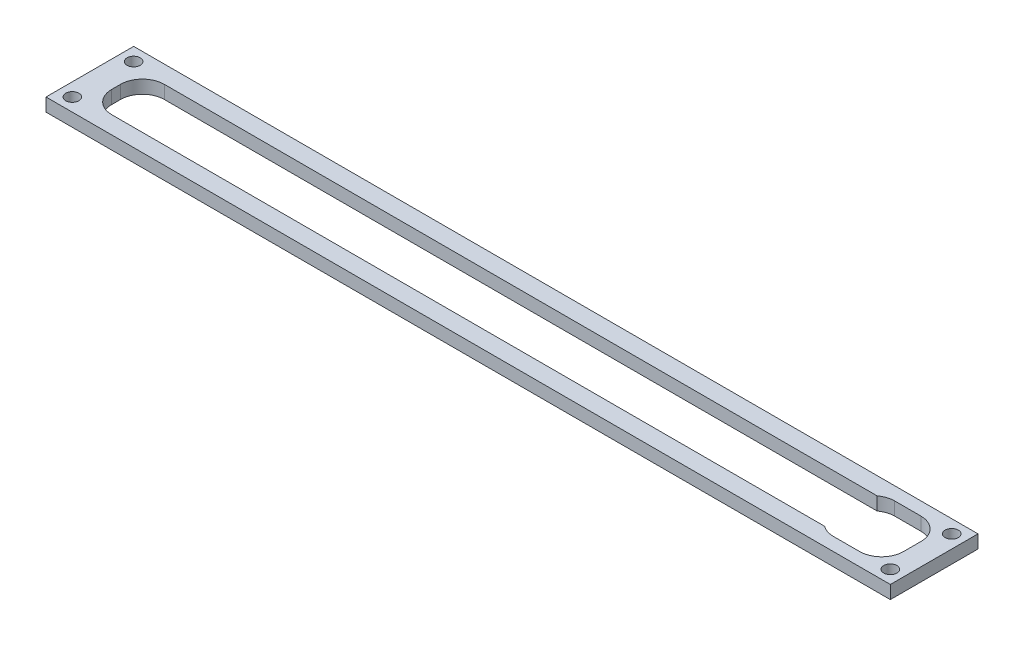
SolidWorks part; units mm, degrees
ref_plane "Front Plane" through (0, 0, 0) normal (0, 0, 1) x (1, 0, 0)
ref_plane "Top Plane" through (0, 0, 0) normal (0, 1, 0) x (1, 0, 0)
ref_plane "Right Plane" through (0, 0, 0) normal (1, 0, 0) x (0, 0, -1)
sketch "Sketch1" plane through (0, 0, 0) normal (0, 1, 0) x (1, 0, 0)
  line L0 (96.3209, 20) -> (96.3209, 0) construction
  line L1 (0, 0) -> (192.6417, 0)
  line L2 (0, 0) -> (0, 20)
  line L3 (0, 20) -> (192.6417, 20)
  line L4 (192.6417, 0) -> (192.6417, 20)
  line L5 (0, 10) -> (192.6417, 10) construction
  line L6 (96.3209, 16) -> (96.3209, 4) construction
  line L7 (6, 16) -> (186.6417, 16)
  line L8 (6, 16) -> (6, 4)
  line L9 (6, 4) -> (186.6417, 4)
  line L10 (186.6417, 16) -> (186.6417, 4)
  line L11 (6, 10) -> (186.6417, 10) construction
  circle A0 centre (3, 17) radius 1.5
  circle A1 centre (3, 3) radius 1.5
  circle A2 centre (189.6417, 3) radius 1.5
  circle A3 centre (189.6417, 17) radius 1.5
  point P17 (96.3209, 10)
  point P18 (96.3209, 10)
  dimension "D7" = 3
  dimension "D1" = 192.6417
  dimension "D2" = 20
  dimension "D3" = 180.6417
  dimension "D4" = 12
  dimension "D5" = 3
  dimension "D6" = 3
extrude "Boss-Extrude1" add sketch "Sketch1" along normal blind 3
sketch "Sketch2" plane through (0, 3, 0) normal (0, 1, 0) x (1, 0, 0)
  line L0 (92, 10) -> (-49908, 10) construction
  line L1 (186.6417, 4) -> (186.6417, 16) construction
  line L2 (173.6417, 17) -> (173.6417, 16)
  line L5 (186.6417, 16) -> (6, 16) construction
  line L6 (180.6417, 17) -> (180.6417, 3) construction
  line L7 (173.6417, 17) -> (187.6417, 17)
  line L9 (173.6417, 3) -> (187.6417, 3)
  line L10 (187.6417, 17) -> (187.6417, 3)
  line L12 (173.6417, 16) -> (186.6417, 16)
  line L13 (186.6417, 16) -> (186.6417, 4)
  line L14 (186.6417, 4) -> (173.6417, 4)
  line L15 (6, 4) -> (186.6417, 4) construction
  line L16 (173.6417, 4) -> (173.6417, 3)
  point P4 (186.6417, 10)
  point P23 (180.6417, 10)
  dimension "D1" = 1
  dimension "D2" = 14
  dimension "D3" = 14
extrude "Cut-Extrude1" cut sketch "Sketch2" against normal through all
fillet "Fillet1" radius 5 6 edges at (187.6417, 1.5, -17) (187.6417, 1.5, -3) (173.6417, 1.5, -17) (173.6417, 1.5, -3) (6, 1.5, -4) (6, 1.5, -16)
equation "\"TrackLength\"= ( ( \"n\" * 28 ) ) / cos ( \"MountAngle\" ) - ( 2 * \"x\" )"
equation "\"D1@Sketch1\"=\"TrackLength\""
equation "\"TrackWidth\"= \"MarbleTrackWidth\" + ( 2 * 4 )"
equation "\"D2@Sketch1\"=\"TrackWidth\""
equation "\"MarbleTrackWidth\"= \"MarbleWidth\" - 1"
equation "\"MarbleTrackLength\"= \"TrackLength\" - ( 2 * 6 )"
equation "\"D3@Sketch1\"=\"MarbleTrackLength\""
equation "\"D4@Sketch1\"=\"MarbleTrackWidth\""
equation "\"MarbleWidth\"= 13"
equation "\"n\"= 7"
equation "\"MountAngle\"= 5"
equation "\"x\"= 14 / cos ( \"MountAngle\" ) - 12"
